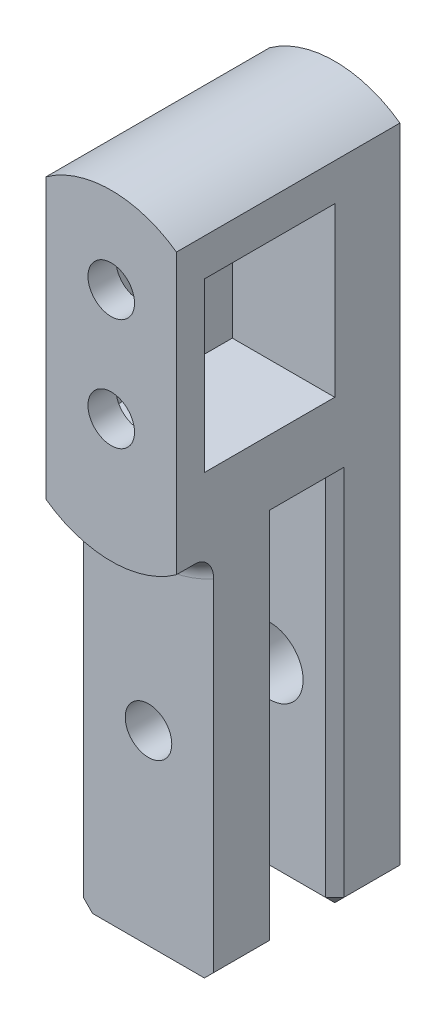
SolidWorks part; units mm, degrees
ref_plane "Front Plane" through (0, 0, 0) normal (0, 0, 1) x (1, 0, 0)
ref_plane "Top Plane" through (0, 0, 0) normal (0, 1, 0) x (1, 0, 0)
ref_plane "Right Plane" through (0, 0, 0) normal (1, 0, 0) x (0, 0, -1)
sketch "Sketch1" plane through (0, 0, 0) normal (0, 0, 1) x (1, 0, 0)
  line L1 (0, 0) -> (7, 0)
  line L2 (0, 0) -> (0, -35)
  line L3 (0, -35) -> (7, -35)
  line L4 (7, 0) -> (7, -35)
extrude "Boss-Extrude1" add sketch "Sketch1" along normal blind 3.5
sketch "Sketch2" plane through (0, 0, 3.5) normal (0, 0, 1) x (1, 0, 0)
  line L0 (0, 0) -> (0, -15)
  line L1 (0, 0) -> (0, -35) construction
  line L2 (0, -15) -> (7, -15)
  line L3 (7, -35) -> (7, 0) construction
  line L4 (7, -15) -> (7, 0)
  line L5 (7, 0) -> (0, 0)
extrude "Boss-Extrude2" add sketch "Sketch2" along normal blind 3
sketch "Sketch3" plane through (0, 0, 6.5) normal (0, 0, 1) x (1, 0, 0)
  line L1 (0, 0) -> (7, 0)
  line L2 (0, 0) -> (0, -35)
  line L3 (0, -35) -> (7, -35)
  line L4 (7, 0) -> (7, -35)
extrude "Boss-Extrude3" add sketch "Sketch3" along normal blind 3.5
sketch "Sketch4" plane through (0, 0, 10) normal (0, 0, 1) x (1, 0, 0)
  line L1 (0, 0) -> (7, 0)
  line L2 (0, 0) -> (0, -15)
  line L3 (0, -15) -> (7, -15)
  line L4 (7, 0) -> (7, -15)
extrude "Boss-Extrude4" add sketch "Sketch4" along normal blind 2
sketch "Sketch5" plane through (0, 0, 0) normal (-1, 0, 0) x (0, 0, 1)
  line L1 (3.5, -2) -> (10.5, -2)
  line L2 (3.5, -2) -> (3.5, -11)
  line L3 (3.5, -11) -> (10.5, -11)
  line L4 (10.5, -2) -> (10.5, -11)
  line L5 (12, 0) -> (0, 0) construction
  line L6 (12, 0) -> (12, -15) construction
  dimension "D1" = 9
  dimension "D2" = 7
  dimension "D3" = 1.5
  dimension "D4" = 2
extrude "Cut-Extrude1" cut sketch "Sketch5" against normal blind 5.5 from offset 1.5 offset against normal yes
sketch "Sketch6" plane through (7, 0, 0) normal (-1, 0, 0) x (0, 0, 1)
  line L0 (6.5, -2) -> (6.5, -11) construction
  line L4 (10.5, -2) -> (3.5, -2) construction
  line L5 (10.5, -11) -> (10.5, -2) construction
  line L6 (3.5, -11) -> (10.5, -11) construction
  circle A0 centre (6.5, -3.5) radius 0.75
  circle A1 centre (6.5, -9.5) radius 0.75
  circle A2 centre (6.5, -6.5) radius 0.75
  dimension "D2" = 1.5
  dimension "D4" = 4.5
  dimension "D1" = 4
  dimension "D3" = 1.5
extrude "Cut-Extrude2" cut sketch "Sketch6" along normal up to next
sketch "Sketch7" plane through (0, 0, 12) normal (0, 0, 1) x (1, 0, 0)
  line L0 (3.5, 0) -> (3.5, -15) construction
  line L1 (7, 0) -> (0, 0) construction
  line L2 (0, -15) -> (7, -15) construction
  line L3 (0, -2) -> (7, -2) construction
  line L4 (7, -15) -> (7, 0) construction
  circle A0 centre (3.5, -3.5) radius 1.25
  circle A1 centre (3.5, -9.5) radius 1.25
  dimension "D2" = 7.5
  dimension "D1" = 1.5
extrude "Cut-Extrude3" cut sketch "Sketch7" against normal up to next
sketch "Sketch9" plane through (0, 0, 12) normal (0, 0, 1) x (1, 0, 0)
  line L0 (0, 0) -> (7, 0)
  arc A0 (7, 0) -> (0, 0) centre (3.5, -4.8734) ccw
extrude "Boss-Extrude5" add sketch "Sketch9" against normal up to surface (12 mm away) up to face at (3.5, -17.5, 0)
sketch "Sketch10" plane through (0, 0, 12) normal (0, 0, 1) x (1, 0, 0)
  line L0 (0, -15) -> (7, -15)
  arc A0 (0, -15) -> (7, -15) centre (3.5, -10.1266) ccw
extrude "Boss-Extrude6" add sketch "Sketch10" against normal up to surface (2 mm away) up to face at (3.5, -25, 10)
chamfer "Chamfer1" distance 0.5 angle 45 12 edges at (0, -25, 3.5) (0, -15, 5) (0, -25, 6.5) (7, -35, 8.25) (0, -35, 8.25) (3.5, -35, 6.5) (0, -35, 1.75) (3.5, -35, 3.5) (7, -35, 1.75) (7, -25, 6.5) (7, -25, 3.5) (7, -15, 5)
sketch "Sketch11" plane through (0, 0, 10) normal (0, 0, 1) x (1, 0, 0)
  line L0 (3.5, -35) -> (3.5, -16.1266) construction
  line L1 (0.5, -35) -> (6.5, -35) construction
  arc A0 (0, -15) -> (7, -15) centre (3.5, -10.1266) ccw construction
  circle A1 centre (3.5, -25) radius 1.25
  dimension "D1" = 10
extrude "Cut-Extrude4" cut sketch "Sketch11" against normal up to next
sketch "Sketch12" plane through (0, 0, 0) normal (0, 0, -1) x (-1, 0, 0)
  line L0 (-3.5, -35) -> (-3.5, -18.8417) construction
  line L1 (-0.5, -35) -> (-6.5, -35) construction
  circle A0 centre (-3.5, -25) radius 1.8
  dimension "D1" = 10
extrude "Cut-Extrude5" cut sketch "Sketch12" against normal up to next
fillet "Fillet1" radius 1 1 edges at (3.5, -16.1266, 10)
